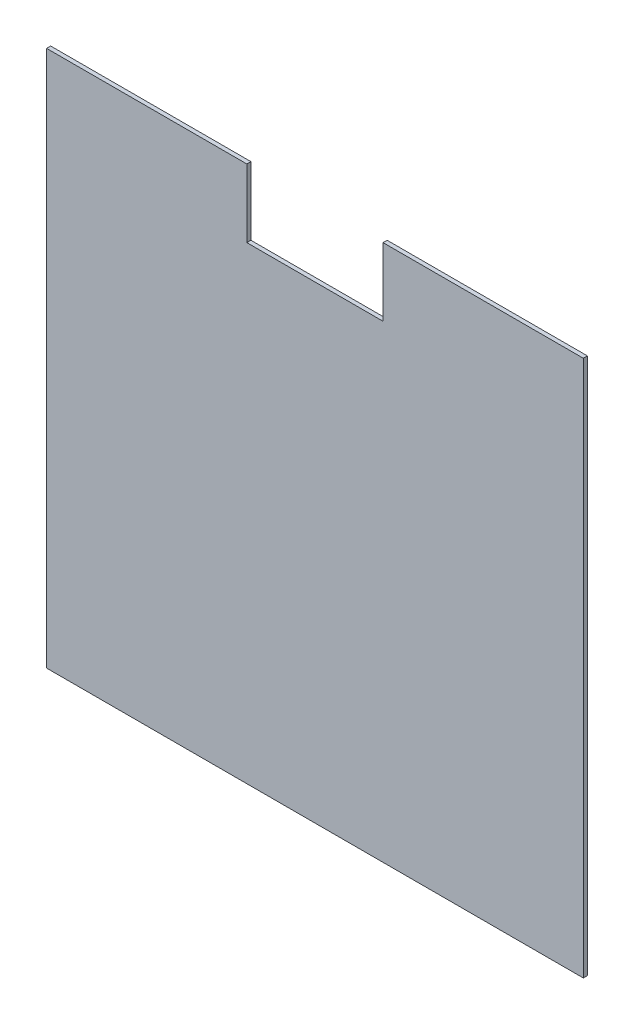
SolidWorks part; units mm, degrees
ref_plane "Piano frontale" through (0, 0, 0) normal (0, 0, 1) x (1, 0, 0)
ref_plane "Piano superiore" through (0, 0, 0) normal (0, 1, 0) x (1, 0, 0)
ref_plane "Piano destro" through (0, 0, 0) normal (1, 0, 0) x (0, 0, -1)
sketch "Schizzo1" plane through (0, 0, 0) normal (0, 0, 1) x (1, 0, 0)
  line L0 (0, 0) -> (0, 394)
  line L1 (0, 394) -> (147, 394)
  line L2 (394, 394) -> (394, 0)
  line L3 (394, 0) -> (0, 0)
  line L4 (147, 394) -> (147, 344)
  line L5 (147, 344) -> (247, 344)
  line L6 (247, 344) -> (247, 394)
  line L7 (247, 394) -> (394, 394)
  dimension "D1" = 394
  dimension "D2" = 394
  dimension "D3" = 100
  dimension "D4" = 50
extrude "Estrusione-Estrusione1" add sketch "Schizzo1" along normal blind 3
